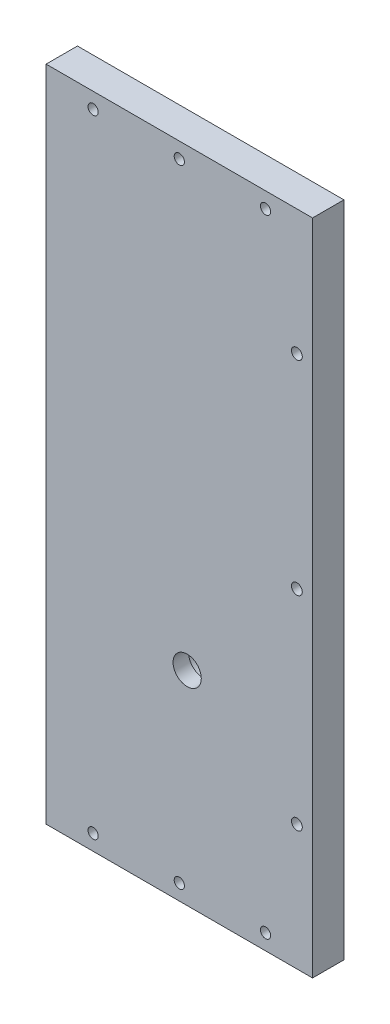
SolidWorks part; units mm, degrees
ref_plane "Front Plane" through (0, 0, 0) normal (0, 0, 1) x (1, 0, 0)
ref_plane "Top Plane" through (0, 0, 0) normal (0, 1, 0) x (1, 0, 0)
ref_plane "Right Plane" through (0, 0, 0) normal (1, 0, 0) x (0, 0, -1)
sketch "Sketch1" plane through (0, 0, 0) normal (0, 0, 1) x (1, 0, 0)
  line L1 (-158.3632, 91.8414) -> (-73.3632, 91.8414)
  line L2 (-158.3632, 91.8414) -> (-158.3632, -118.1586)
  line L3 (-158.3632, -118.1586) -> (-73.3632, -118.1586)
  line L4 (-73.3632, 91.8414) -> (-73.3632, -118.1586)
  dimension "D1" = 210
  dimension "D2" = 85
extrude "Boss-Extrude1" add sketch "Sketch1" along normal blind 10
sketch "Sketch4" plane through (0, 0, 0) normal (0, 0, -1) x (-1, 0, 0)
  line L0 (73.3632, -13.1586) -> (158.3632, -13.1586)
  line L1 (73.3632, -118.1586) -> (73.3632, 91.8414) construction
  line L2 (158.3632, 91.8414) -> (158.3632, -118.1586) construction
  line L3 (78.3632, -78.1586) -> (78.3632, 51.8414)
  line L4 (73.3632, -118.1586) -> (73.3632, 91.8414) construction
  point P9 (78.3632, -13.1586)
  dimension "D1" = 130
  dimension "D2" = 5
hole_wizard "CBORE for #4 Binding Head Machine Screw1" positions "Sketch5" profile "Sketch6" counterbore size "#4" standard "ANSI Inch" end condition through all
sketch "Sketch5" plane through (0, 0, 0) normal (0, 0, -1) x (-1, 0, 0)
  line L0 (78.3632, -78.1586) -> (78.3632, 51.8414) construction
  point P0 (78.3632, 51.8414)
  point P3 (78.3632, -13.1586)
  point P7 (78.3632, -78.1586)
sketch "Sketch6" plane through (-78.3632, 51.8414, 0) normal (1, 0, 0) x (0, 1, 0)
  line L0 (0, 0) -> (0, 10)
  line L1 (0, 10) -> (1.7272, 10)
  line L3 (1.7272, 10) -> (1.7272, 1.7272)
  line L4 (1.7272, 1.7272) -> (3.3731, 1.7272)
  line L5 (3.3731, 1.7272) -> (3.3731, 0)
  line L7 (3.3731, 0) -> (0, 0)
  line L11 (0, -6.35) -> (0, 107.95) construction
  dimension "Thru Hole Dia." = 3.4544
  dimension "Thru Hole Depth" = 10
  dimension "C'Bore Dia." = 6.7462
  dimension "C'Bore Depth" = 1.7272
sketch "Sketch7" plane through (0, 0, 0) normal (0, 0, -1) x (-1, 0, 0)
  line L0 (88.3632, -113.1586) -> (143.3632, -113.1586)
  line L1 (158.3632, -118.1586) -> (73.3632, -118.1586) construction
  line L2 (73.3632, -118.1586) -> (73.3632, 91.8414) construction
  line L3 (73.3632, -13.1586) -> (158.3632, -13.1586)
  line L4 (88.3632, 86.8414) -> (143.3632, 86.8414)
  point P3 (115.8632, -113.1586)
  point P7 (115.8632, -118.1586)
  dimension "D1" = 5
  dimension "D2" = 15
  dimension "D3" = 0
hole_wizard "CBORE for #4 Binding Head Machine Screw2" positions "Sketch8" profile "Sketch9" counterbore size "#4" standard "ANSI Inch" end condition up to next
sketch "Sketch8" plane through (0, 0, 0) normal (0, 0, -1) x (-1, 0, 0)
  line L0 (88.3632, 86.8414) -> (143.3632, 86.8414) construction
  line L1 (88.3632, -113.1586) -> (143.3632, -113.1586) construction
  point P0 (88.3632, 86.8414)
  point P3 (115.8632, 86.8414)
  point P7 (143.3632, 86.8414)
  point P10 (143.3632, -113.1586)
  point P13 (115.8632, -113.1586)
  point P17 (88.3632, -113.1586)
sketch "Sketch9" plane through (-88.3632, 86.8414, 0) normal (1, 0, 0) x (0, 1, 0)
  line L0 (0, 0) -> (0, 10)
  line L1 (0, 10) -> (1.6319, 10)
  line L3 (1.6319, 10) -> (1.632, 1.7272)
  line L4 (1.632, 1.7272) -> (3.3731, 1.7272)
  line L5 (3.3731, 1.7272) -> (3.3731, 0)
  line L7 (3.3731, 0) -> (0, 0)
  line L11 (0, -6.35) -> (0, 107.95) construction
  dimension "Thru Hole Dia." = 3.2639
  dimension "Thru Hole Depth" = 10
  dimension "C'Bore Dia." = 6.7462
  dimension "C'Bore Depth" = 1.7272
sketch "Sketch10" plane through (0, 0, 0) normal (0, 0, -1) x (-1, 0, 0)
  line L1 (73.3632, -118.1586) -> (73.3632, 91.8414) construction
  line L2 (73.3632, -13.1586) -> (158.3632, -13.1586) construction
  circle A0 centre (113.3632, -53.1586) radius 6.35
  circle A1 centre (113.3632, -53.1586) radius 4.5
  dimension "D2" = 12.7
  dimension "D4" = 9
  dimension "D1" = 40
  dimension "D3" = 40
extrude "Cut-Extrude1" cut sketch "Sketch10" against normal blind 5
extrude "Cut-Extrude3" cut sketch "Sketch10<3>" against normal up to next contours A1 region at (-113.3632, -53.1586, 0)
sketch "Sketch10<3>" plane through (0, 0, 0) normal (0, 0, -1) x (-1, 0, 0) same geometry as "Sketch10"
sketch "Sketch11" plane through (-158.3632, 0, 0) normal (-1, 0, 0) x (0, 0, 1)
  line L0 (5, 91.8414) -> (5, -118.1586)
  line L1 (10, 91.8414) -> (0, 91.8414) construction
  line L2 (10, -118.1586) -> (0, -118.1586) construction
  line L3 (0, -13.1586) -> (10, -13.1586)
  line L4 (10, 91.8414) -> (10, -118.1586) construction
  point P11 (5, 36.8414)
  point P12 (5, -63.1586)
  dimension "D1" = 50
hole_wizard "#4-40 Tapped Hole2" positions "Sketch14" profile "Sketch15" tap size "#4-40" standard "ANSI Inch"
sketch "Sketch14" plane through (-158.3632, 0, 0) normal (-1, 0, 0) x (0, 0, 1)
  point P0 (5, -63.1586)
  point P3 (5, 36.8414)
sketch "Sketch15" plane through (-158.3632, -63.1586, 5) normal (0, 1, 0) x (0, 0, 1)
  line L0 (0, 0) -> (0, 8.2792)
  line L1 (0, 8.2792) -> (1.1303, 7.6)
  line L2 (1.1303, 7.6) -> (1.1303, 0)
  line L5 (1.1303, 0) -> (0, 0)
  line L10 (0, 8.2792) -> (-1.1303, 7.6) construction
  line L11 (0, -6.35) -> (0, 107.95) construction
  dimension "Tap Drill Dia." = 2.2606
  dimension "Tap Drill Depth" = 7.6
  dimension "Drill Angle" = 118
cosmetic thread "Hole Thread3" parameters "D1"=5.69, "D2"=2.8448
cosmetic thread "Hole Thread4" parameters "D1"=5.69, "D2"=2.8448
